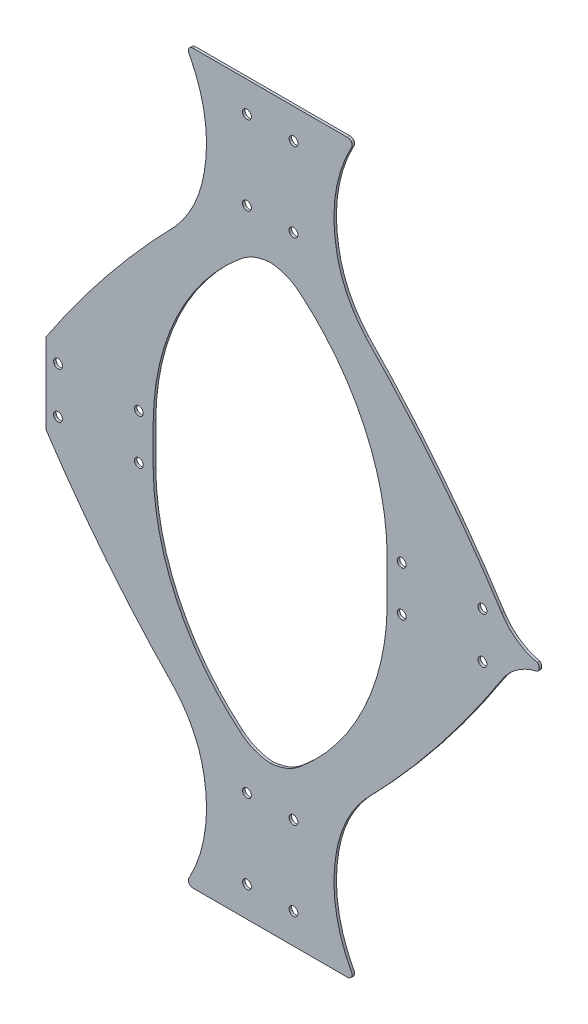
SolidWorks part; units mm, degrees
ref_plane "Front Plane" through (0, 0, 0) normal (0, 0, 1) x (1, 0, 0)
ref_plane "Top Plane" through (0, 0, 0) normal (0, 1, 0) x (1, 0, 0)
ref_plane "Right Plane" through (0, 0, 0) normal (1, 0, 0) x (0, 0, -1)
sketch "Model" plane through (0, 0, 0) normal (0, 0, 1) x (1, 0, 0)
  line B0 (293.8436, -56.5322) -> (293.8436, 0)
  line B1 (0, 914.4) -> (194.4798, 914.4)
  line B2 (293.8436, 56.5322) -> (293.8436, 0)
  line B3 (0, 914.4) -> (-194.4798, 914.4)
  line B4 (0, 545.0832) -> (0, 0) construction
  line B5 (0, 0) -> (293.8436, 0) construction
  arc B6 (239.6834, -503.1053) -> (187.9198, -583.3951) centre (465.825, -705.7322) ccw
  arc B7 (239.6834, -503.1053) -> (582.0374, -72.7477) centre (-1699.953, 1391.2476) ccw
  arc B8 (671.3071, -9.5736) -> (582.0374, -72.7477) centre (702.2766, -147.9952) ccw
  arc B9 (671.3071, -9.5736) -> (676.2743, 0) centre (664.8452, -0.1455) ccw
  arc B10 (101.6984, -491.6043) -> (294.1166, -52.0761) centre (-316.104, -46.8144) ccw
  circle B11 centre (330.3561, -56.5322) radius 11.1125
  circle B12 centre (533.5906, -57.7678) radius 11.1125
  arc B13 (202.9832, 895.3321) -> (194.4798, 914.4) centre (194.4798, 902.97) ccw
  arc B14 (202.9832, 895.3321) -> (165.892, 658.247) centre (527.5303, 723.1138) ccw
  arc B15 (165.9389, 658.1298) -> (239.6834, 503.1053) centre (465.825, 705.7322) ccw
  arc B16 (582.0374, 72.7477) -> (239.6834, 503.1053) centre (-1699.953, -1391.2476) ccw
  arc B17 (582.0374, 72.7477) -> (671.3071, 9.5736) centre (702.2766, 147.9952) ccw
  arc B18 (676.2743, 0) -> (671.3071, 9.5736) centre (664.8452, 0.1455) ccw
  arc B19 (294.1166, 52.0761) -> (76.1318, 514.3055) centre (-316.104, 46.8144) ccw
  arc B20 (76.1318, 514.3055) -> (0, 545.0832) centre (-7, 418.2194) ccw
  circle B21 centre (58.5418, 838.2689) radius 11.1125
  circle B22 centre (330.3561, 56.5322) radius 11.1125
  circle B23 centre (533.5906, 57.7678) radius 11.1125
  circle B24 centre (58.5418, 639.4053) radius 11.1125
  arc B25 (-194.4798, 914.4) -> (-202.9832, 895.3321) centre (-194.4798, 902.97) ccw
  arc B26 (-165.892, 658.247) -> (-202.9832, 895.3321) centre (-527.5303, 723.1138) ccw
  arc B27 (-187.9198, 583.3951) -> (-165.9389, 658.1298) centre (-465.825, 705.7322) ccw
  arc B28 (-76.1318, 514.3055) -> (-101.6984, 491.6043) centre (316.104, 46.8144) ccw
  arc B29 (0, 545.0832) -> (-76.1318, 514.3055) centre (7, 418.2194) ccw
  circle B30 centre (-58.5418, 838.2689) radius 11.1125
  circle B31 centre (-58.5418, 639.4053) radius 11.1125
  line B32 (-293.8436, 56.5322) -> (-293.8436, 0)
  line B33 (0, -914.4) -> (-194.4798, -914.4)
  line B34 (-293.8436, -56.5322) -> (-293.8436, 0)
  line B35 (0, -914.4) -> (194.4798, -914.4)
  line B36 (0, -545.0832) -> (0, 0) construction
  line B37 (0, 0) -> (-293.8436, 0) construction
  arc B38 (-239.6834, 503.1053) -> (-187.9198, 583.3951) centre (-465.825, 705.7322) ccw
  arc B39 (-239.6834, 503.1053) -> (-582.0374, 72.7477) centre (1699.953, -1391.2476) ccw
  arc B40 (-671.3071, 9.5736) -> (-582.0374, 72.7477) centre (-702.2766, 147.9952) ccw
  arc B41 (-671.3071, 9.5736) -> (-676.2743, 0) centre (-664.8452, 0.1455) ccw
  arc B42 (-101.6984, 491.6043) -> (-294.1166, 52.0761) centre (316.104, 46.8144) ccw
  circle B43 centre (-330.3561, 56.5322) radius 11.1125
  circle B44 centre (-533.5906, 57.7678) radius 11.1125
  arc B45 (-202.9832, -895.3321) -> (-194.4798, -914.4) centre (-194.4798, -902.97) ccw
  arc B46 (-202.9832, -895.3321) -> (-165.892, -658.247) centre (-527.5303, -723.1138) ccw
  arc B47 (-165.9389, -658.1298) -> (-239.6834, -503.1053) centre (-465.825, -705.7322) ccw
  arc B48 (-582.0374, -72.7477) -> (-239.6834, -503.1053) centre (1699.953, 1391.2476) ccw
  arc B49 (-582.0374, -72.7477) -> (-671.3071, -9.5736) centre (-702.2766, -147.9952) ccw
  arc B50 (-676.2743, 0) -> (-671.3071, -9.5736) centre (-664.8452, -0.1455) ccw
  arc B51 (-294.1166, -52.0761) -> (-76.1318, -514.3055) centre (316.104, -46.8144) ccw
  arc B52 (-76.1318, -514.3055) -> (0, -545.0832) centre (7, -418.2194) ccw
  circle B53 centre (-58.5418, -838.2689) radius 11.1125
  circle B54 centre (-330.3561, -56.5322) radius 11.1125
  circle B55 centre (-533.5906, -57.7678) radius 11.1125
  circle B56 centre (-58.5418, -639.4053) radius 11.1125
  arc B57 (194.4798, -914.4) -> (202.9832, -895.3321) centre (194.4798, -902.97) ccw
  arc B58 (165.892, -658.247) -> (202.9832, -895.3321) centre (527.5303, -723.1138) ccw
  arc B59 (187.9198, -583.3951) -> (165.9389, -658.1298) centre (465.825, -705.7322) ccw
  arc B60 (76.1318, -514.3055) -> (101.6984, -491.6043) centre (-316.104, -46.8144) ccw
  arc B61 (0, -545.0832) -> (76.1318, -514.3055) centre (-7, -418.2194) ccw
  circle B62 centre (58.5418, -838.2689) radius 11.1125
  circle B63 centre (58.5418, -639.4053) radius 11.1125
sketch_block_instance "Block1-1"
sketch_block "Block1"
sketch_block_instance "Block1-2"
sketch "Sketch2" plane through (0, 0, 0) normal (0, 0, 1) x (1, 0, 0)
  line L0 (0, 914.4) -> (-194.4798, 914.4) construction
  line L1 (0, 914.4) -> (194.4798, 914.4) construction
  line L2 (0, -914.4) -> (-194.4798, -914.4) construction
  line L3 (0, -914.4) -> (194.4798, -914.4) construction
  line L4 (0, 914.4) -> (-194.4798, 914.4)
  line L5 (0, 914.4) -> (194.4798, 914.4)
  line L6 (0, -914.4) -> (-194.4798, -914.4)
  line L7 (0, -914.4) -> (194.4798, -914.4)
  line L8 (294.1166, 52.0761) -> (294.1166, -52.0761)
  line L9 (-294.1166, -52.0761) -> (-294.1166, 52.0761)
  line L10 (-165.9389, 658.1298) -> (-165.892, 658.247)
  line L11 (165.892, 658.247) -> (165.9389, 658.1298)
  line L12 (165.892, -658.247) -> (165.9389, -658.1298)
  line L13 (-165.892, -658.247) -> (-165.9389, -658.1298)
  arc A0 (582.0374, 72.7477) -> (239.6834, 503.1053) centre (-1699.953, -1391.2476) ccw construction
  arc A1 (165.9389, 658.1298) -> (239.6834, 503.1053) centre (465.825, 705.7322) ccw construction
  arc A2 (202.9832, 895.3321) -> (165.892, 658.247) centre (527.5303, 723.1138) ccw construction
  arc A3 (202.9832, 895.3321) -> (194.4798, 914.4) centre (194.4798, 902.97) ccw construction
  arc A4 (-194.4798, 914.4) -> (-202.9832, 895.3321) centre (-194.4798, 902.97) ccw construction
  arc A5 (-165.892, 658.247) -> (-202.9832, 895.3321) centre (-527.5303, 723.1138) ccw construction
  arc A6 (-187.9198, 583.3951) -> (-165.9389, 658.1298) centre (-465.825, 705.7322) ccw construction
  arc A7 (-239.6834, 503.1053) -> (-187.9198, 583.3951) centre (-465.825, 705.7322) ccw construction
  arc A8 (-239.6834, 503.1053) -> (-582.0374, 72.7477) centre (1699.953, -1391.2476) ccw construction
  arc A9 (-671.3071, 9.5736) -> (-582.0374, 72.7477) centre (-702.2766, 147.9952) ccw construction
  arc A10 (-671.3071, 9.5736) -> (-676.2743, 0) centre (-664.8452, 0.1455) ccw construction
  arc A11 (-676.2743, 0) -> (-671.3071, -9.5736) centre (-664.8452, -0.1455) ccw construction
  arc A12 (-582.0374, -72.7477) -> (-671.3071, -9.5736) centre (-702.2766, -147.9952) ccw construction
  arc A13 (-582.0374, -72.7477) -> (-239.6834, -503.1053) centre (1699.953, 1391.2476) ccw construction
  arc A14 (-165.9389, -658.1298) -> (-239.6834, -503.1053) centre (-465.825, -705.7322) ccw construction
  arc A15 (-202.9832, -895.3321) -> (-165.892, -658.247) centre (-527.5303, -723.1138) ccw construction
  arc A16 (-202.9832, -895.3321) -> (-194.4798, -914.4) centre (-194.4798, -902.97) ccw construction
  arc A17 (194.4798, -914.4) -> (202.9832, -895.3321) centre (194.4798, -902.97) ccw construction
  arc A18 (165.892, -658.247) -> (202.9832, -895.3321) centre (527.5303, -723.1138) ccw construction
  arc A19 (187.9198, -583.3951) -> (165.9389, -658.1298) centre (465.825, -705.7322) ccw construction
  arc A20 (239.6834, -503.1053) -> (187.9198, -583.3951) centre (465.825, -705.7322) ccw construction
  arc A21 (239.6834, -503.1053) -> (582.0374, -72.7477) centre (-1699.953, 1391.2476) ccw construction
  arc A22 (582.0374, 72.7477) -> (671.3071, 9.5736) centre (702.2766, 147.9952) ccw construction
  arc A23 (676.2743, 0) -> (671.3071, 9.5736) centre (664.8452, 0.1455) ccw construction
  arc A24 (671.3071, -9.5736) -> (676.2743, 0) centre (664.8452, -0.1455) ccw construction
  arc A25 (671.3071, -9.5736) -> (582.0374, -72.7477) centre (702.2766, -147.9952) ccw construction
  arc A26 (-294.1166, -52.0761) -> (-76.1318, -514.3055) centre (316.104, -46.8144) ccw construction
  arc A27 (-101.6984, 491.6043) -> (-294.1166, 52.0761) centre (316.104, 46.8144) ccw construction
  arc A28 (-76.1318, 514.3055) -> (-101.6984, 491.6043) centre (316.104, 46.8144) ccw construction
  arc A29 (0, 545.0832) -> (-76.1318, 514.3055) centre (7, 418.2194) ccw construction
  arc A30 (76.1318, 514.3055) -> (0, 545.0832) centre (-7, 418.2194) ccw construction
  arc A31 (294.1166, 52.0761) -> (76.1318, 514.3055) centre (-316.104, 46.8144) ccw construction
  arc A32 (101.6984, -491.6043) -> (294.1166, -52.0761) centre (-316.104, -46.8144) ccw construction
  arc A33 (0, -545.0832) -> (76.1318, -514.3055) centre (-7, -418.2194) ccw construction
  arc A34 (-76.1318, -514.3055) -> (0, -545.0832) centre (7, -418.2194) ccw construction
  arc A35 (76.1318, -514.3055) -> (101.6984, -491.6043) centre (-316.104, -46.8144) ccw construction
  circle A36 centre (-58.5418, -639.4053) radius 11.1125 construction
  circle A37 centre (-58.5418, -838.2689) radius 11.1125 construction
  circle A38 centre (58.5418, -838.2689) radius 11.1125 construction
  circle A39 centre (58.5418, -639.4053) radius 11.1125 construction
  circle A40 centre (533.5906, -57.7678) radius 11.1125 construction
  circle A41 centre (330.3561, -56.5322) radius 11.1125 construction
  circle A42 centre (330.3561, 56.5322) radius 11.1125 construction
  circle A43 centre (533.5906, 57.7678) radius 11.1125 construction
  circle A44 centre (58.5418, 838.2689) radius 11.1125 construction
  circle A45 centre (-58.5418, 838.2689) radius 11.1125 construction
  circle A46 centre (-58.5418, 639.4053) radius 11.1125 construction
  circle A47 centre (58.5418, 639.4053) radius 11.1125 construction
  circle A48 centre (-330.3561, -56.5322) radius 11.1125 construction
  circle A49 centre (-330.3561, 56.5322) radius 11.1125 construction
  circle A50 centre (-533.5906, 57.7678) radius 11.1125 construction
  circle A51 centre (-533.5906, -57.7678) radius 11.1125 construction
  arc A52 (582.0374, 72.7477) -> (239.6834, 503.1053) centre (-1699.953, -1391.2476) ccw
  arc A53 (165.9389, 658.1298) -> (239.6834, 503.1053) centre (465.825, 705.7322) ccw
  arc A54 (202.9832, 895.3321) -> (165.892, 658.247) centre (527.5303, 723.1138) ccw
  arc A55 (202.9832, 895.3321) -> (194.4798, 914.4) centre (194.4798, 902.97) ccw
  arc A56 (-194.4798, 914.4) -> (-202.9832, 895.3321) centre (-194.4798, 902.97) ccw
  arc A57 (-165.892, 658.247) -> (-202.9832, 895.3321) centre (-527.5303, 723.1138) ccw
  arc A58 (-187.9198, 583.3951) -> (-165.9389, 658.1298) centre (-465.825, 705.7322) ccw
  arc A59 (-239.6834, 503.1053) -> (-187.9198, 583.3951) centre (-465.825, 705.7322) ccw
  arc A60 (-239.6834, 503.1053) -> (-582.0374, 72.7477) centre (1699.953, -1391.2476) ccw
  arc A61 (-671.3071, 9.5736) -> (-582.0374, 72.7477) centre (-702.2766, 147.9952) ccw
  arc A62 (-671.3071, 9.5736) -> (-676.2743, 0) centre (-664.8452, 0.1455) ccw
  arc A63 (-676.2743, 0) -> (-671.3071, -9.5736) centre (-664.8452, -0.1455) ccw
  arc A64 (-582.0374, -72.7477) -> (-671.3071, -9.5736) centre (-702.2766, -147.9952) ccw
  arc A65 (-582.0374, -72.7477) -> (-239.6834, -503.1053) centre (1699.953, 1391.2476) ccw
  arc A66 (-165.9389, -658.1298) -> (-239.6834, -503.1053) centre (-465.825, -705.7322) ccw
  arc A67 (-202.9832, -895.3321) -> (-165.892, -658.247) centre (-527.5303, -723.1138) ccw
  arc A68 (-202.9832, -895.3321) -> (-194.4798, -914.4) centre (-194.4798, -902.97) ccw
  arc A69 (194.4798, -914.4) -> (202.9832, -895.3321) centre (194.4798, -902.97) ccw
  arc A70 (165.892, -658.247) -> (202.9832, -895.3321) centre (527.5303, -723.1138) ccw
  arc A71 (187.9198, -583.3951) -> (165.9389, -658.1298) centre (465.825, -705.7322) ccw
  arc A72 (239.6834, -503.1053) -> (187.9198, -583.3951) centre (465.825, -705.7322) ccw
  arc A73 (239.6834, -503.1053) -> (582.0374, -72.7477) centre (-1699.953, 1391.2476) ccw
  arc A74 (582.0374, 72.7477) -> (671.3071, 9.5736) centre (702.2766, 147.9952) ccw
  arc A75 (676.2743, 0) -> (671.3071, 9.5736) centre (664.8452, 0.1455) ccw
  arc A76 (671.3071, -9.5736) -> (676.2743, 0) centre (664.8452, -0.1455) ccw
  arc A77 (671.3071, -9.5736) -> (582.0374, -72.7477) centre (702.2766, -147.9952) ccw
  arc A78 (-294.1166, -52.0761) -> (-76.1318, -514.3055) centre (316.104, -46.8144) ccw
  arc A79 (-101.6984, 491.6043) -> (-294.1166, 52.0761) centre (316.104, 46.8144) ccw
  arc A80 (-76.1318, 514.3055) -> (-101.6984, 491.6043) centre (316.104, 46.8144) ccw
  arc A81 (0, 545.0832) -> (-76.1318, 514.3055) centre (7, 418.2194) ccw
  arc A82 (76.1318, 514.3055) -> (0, 545.0832) centre (-7, 418.2194) ccw
  arc A83 (294.1166, 52.0761) -> (76.1318, 514.3055) centre (-316.104, 46.8144) ccw
  arc A84 (101.6984, -491.6043) -> (294.1166, -52.0761) centre (-316.104, -46.8144) ccw
  arc A85 (0, -545.0832) -> (76.1318, -514.3055) centre (-7, -418.2194) ccw
  arc A86 (-76.1318, -514.3055) -> (0, -545.0832) centre (7, -418.2194) ccw
  arc A87 (76.1318, -514.3055) -> (101.6984, -491.6043) centre (-316.104, -46.8144) ccw
  circle A88 centre (-58.5418, -639.4053) radius 11.1125
  circle A89 centre (-58.5418, -838.2689) radius 11.1125
  circle A90 centre (58.5418, -838.2689) radius 11.1125
  circle A91 centre (58.5418, -639.4053) radius 11.1125
  circle A92 centre (533.5906, -57.7678) radius 11.1125
  circle A93 centre (330.3561, -56.5322) radius 11.1125
  circle A94 centre (330.3561, 56.5322) radius 11.1125
  circle A95 centre (533.5906, 57.7678) radius 11.1125
  circle A96 centre (58.5418, 838.2689) radius 11.1125
  circle A97 centre (-58.5418, 838.2689) radius 11.1125
  circle A98 centre (-58.5418, 639.4053) radius 11.1125
  circle A99 centre (58.5418, 639.4053) radius 11.1125
  circle A100 centre (-330.3561, -56.5322) radius 11.1125
  circle A101 centre (-330.3561, 56.5322) radius 11.1125
  circle A102 centre (-533.5906, 57.7678) radius 11.1125
  circle A103 centre (-533.5906, -57.7678) radius 11.1125
extrude "Boss-Extrude1" add sketch "Sketch2" along normal blind 6.35
sketch "Sketch4" plane through (0, 0, 6.35) normal (0, 0, 1) x (1, 0, 0)
  line L0 (-563.1003, -101.854) -> (-563.1003, 101.854) construction
  line L1 (-563.1003, -101.854) -> (-563.1003, 101.854)
extrude "Cut-Extrude1" cut sketch "Sketch4" against normal through all and the other way through all
